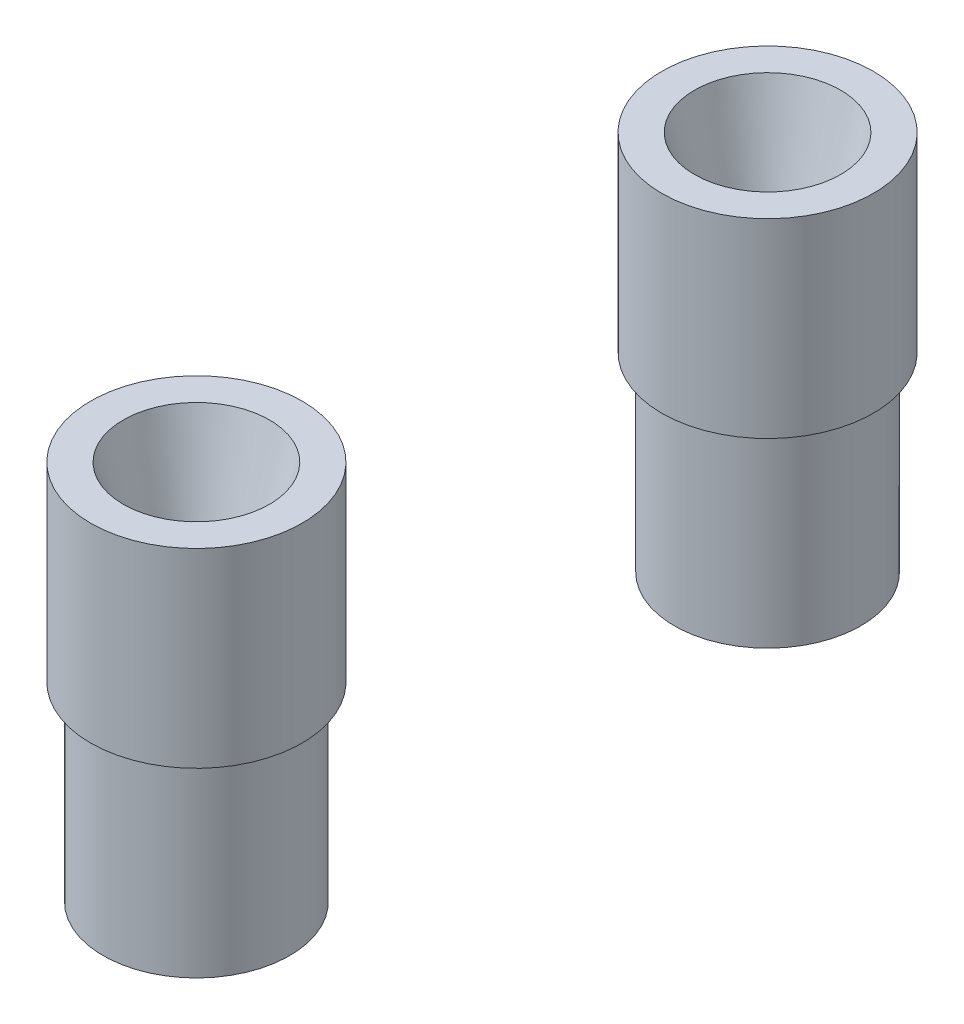
SolidWorks part; units mm, degrees
ref_plane "Front Plane" through (0, 0, 0) normal (0, 0, 1) x (1, 0, 0)
ref_plane "Top Plane" through (0, 0, 0) normal (0, 1, 0) x (1, 0, 0)
ref_plane "Right Plane" through (0, 0, 0) normal (1, 0, 0) x (0, 0, -1)
sketch "Sketch1" plane through (0, 0, 0) normal (0, 0, 1) x (1, 0, 0)
  line L0 (0, 0) -> (0, 20) construction
  line L1 (0, 20) -> (5.5562, 20)
  line L2 (5.5562, 20) -> (5.5562, 10)
  line L3 (5.5562, 10) -> (4.9, 10)
  line L4 (4.9, 10) -> (4.9, 0)
  line L5 (4.9, 0) -> (0, 0)
  line L6 (0, 0) -> (0, 20)
  dimension "D1" = 11.1125
  dimension "D2" = 9.8
  dimension "D3" = 10
  dimension "D4" = 10
revolve "Revolve1" add sketch "Sketch1" angle 360 about L0
sketch "Sketch2" plane through (0, 20, 0) normal (0, 1, 0) x (1, 0, 0)
  circle A0 centre (0, 0) radius 2.5
  dimension "D1" = 5
extrude "Cut-Extrude1" cut sketch "Sketch2" against normal blind 5
draft "Draft1" type of draft neutral plane draft angle 15 faces to draft 1 face at (0, 15, 2.5) neutral plane through (0, 15, 0) neutral plane normal (0, 1, 0) parameters "D1"=15
move or copy body "Body-Move/Copy1" bodies to move or copy 102 copy yes number of copies 1 translate (0, 0, 30)
